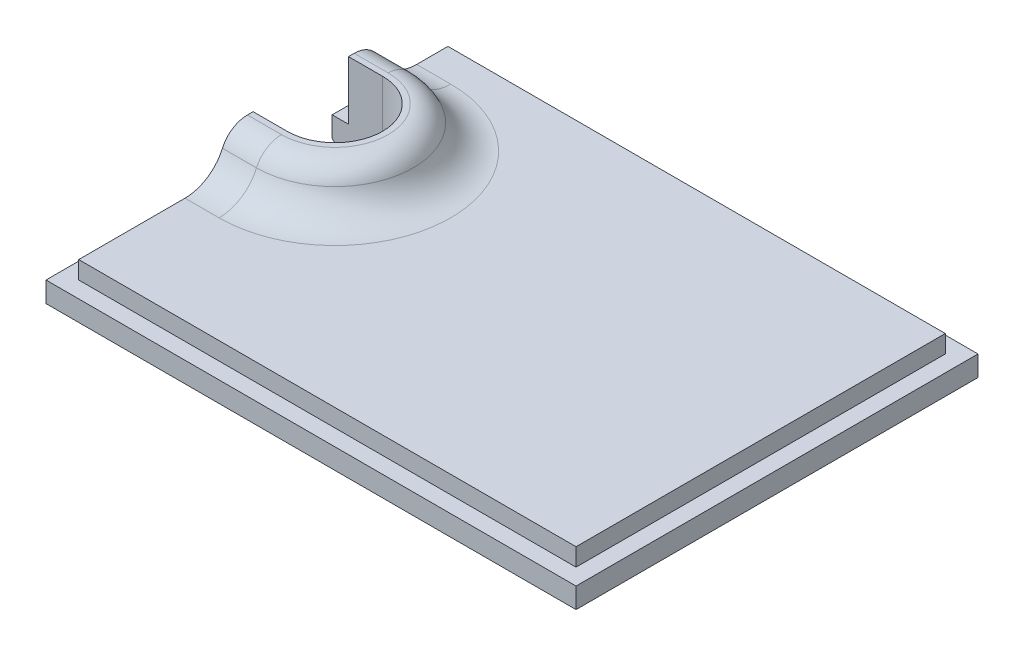
SolidWorks part; units mm, degrees
ref_plane "Front Plane" through (0, 0, 0) normal (0, 0, 1) x (1, 0, 0)
ref_plane "Top Plane" through (0, 0, 0) normal (0, 1, 0) x (1, 0, 0)
ref_plane "Right Plane" through (0, 0, 0) normal (1, 0, 0) x (0, 0, -1)
sketch "Sketch1" plane through (0, 0, 0) normal (0, 1, 0) x (1, 0, 0)
  line L0 (-19.45, 14.75) -> (-19.45, 6.25)
  line L1 (-19.45, -14.75) -> (19.45, -14.75)
  line L2 (19.45, -14.75) -> (19.45, 14.75)
  line L3 (19.45, 14.75) -> (-19.45, 14.75)
  line L4 (18.25, 13.55) -> (-18.25, 13.55)
  line L5 (-18.25, 13.55) -> (-18.25, 6.25)
  line L6 (-18.25, -13.55) -> (18.25, -13.55)
  line L7 (18.25, -13.55) -> (18.25, 13.55)
  line L8 (-18.25, 13.55) -> (0, 0) construction
  line L9 (0, 0) -> (18.25, -13.55) construction
  line L10 (0, 0) -> (18.25, 13.55) construction
  line L11 (0, 0) -> (-18.25, -13.55) construction
  line L12 (-15.75, 8.25) -> (-18.25, 8.25)
  line L13 (-18.25, 8.25) -> (-19.45, 8.25)
  line L14 (-15.75, 6.25) -> (-18.25, 6.25)
  line L15 (-18.25, 6.25) -> (-19.45, 6.25)
  line L16 (-15.75, -0.75) -> (-18.25, -0.75)
  line L17 (-18.25, -0.75) -> (-19.45, -0.75)
  line L18 (-15.75, -2.75) -> (-18.25, -2.75)
  line L19 (-18.25, -2.75) -> (-19.45, -2.75)
  line L20 (-19.45, -0.75) -> (-19.45, -14.75)
  line L21 (-19.45, 14.75) -> (-19.45, -14.75) construction
  line L22 (-18.25, -0.75) -> (-18.25, -13.55)
  line L23 (-18.25, 13.55) -> (-18.25, -13.55) construction
  arc A0 (-15.75, 6.25) -> (-15.75, -0.75) centre (-15.75, 2.75) cw
  arc A1 (-15.75, 8.25) -> (-15.75, -2.75) centre (-15.75, 2.75) cw
  arc A2 (-17.6698, 5.6765) -> (-15.75, -0.75) centre (-15.75, 2.75) cw construction
  arc A3 (-18.7669, 7.3487) -> (-15.75, -2.75) centre (-15.75, 2.75) cw construction
  dimension "D4" = 3.5
  dimension "D6" = 2
  dimension "D1" = 29.5
  dimension "D2" = 38.9
  dimension "D5" = 12
  dimension "D7" = 2.5
  dimension "D3" = 1.2
extrude "Boss-Extrude1" add sketch "Sketch1" along normal blind 1 contours L12 A1 L18 L5 L6 L7 L4 | A1 L12 L5 L14 A0 L16 L18 | L19 L5 L17 L0 | L15 L5 L13 L0 | L5 L19 L0 L1 L2 L3 L13 L4 L7 L6 | L17 L20 L1 L2 L3 L0 L15 L14 A0 L16 | L4 L5 L6 L7 region at (0, 0, -14.2618) region at (-18.85, 0, -7.25) region at (-17, 0, -8.114) region at (1.2088, 0, 0.2257) region at (-18.85, 0, 1.75)
extrude "Boss-Extrude2" add sketch "Sketch1<5>" along normal blind 1.6 from surface contours L5 A1 L6 L7 L4 | A1 L5 A0 | A1 L0 A0 L5 | L0 A1 L5 L4 L7 L6 L1 L2 L3 | A1 L5 A0 L0 | L5 L0 | L5 L0 | L22 L17 L20 L19 region at (0, 0, -14.2618) region at (-18.85, 0, -7.25) region at (-17, 0, -8.114) region at (1.2088, 0, 0.2257) region at (-18.85, 0, 1.75) starting at face at (-8.3625, 1, -1.375)
sketch "Sketch1<5>" plane through (0, 0, 0) normal (0, 1, 0) x (1, 0, 0) same geometry as "Sketch1"
extrude "Boss-Extrude3" add sketch "Sketch1<6>" along normal blind 1.3 from surface contours L5 A1 L6 L7 L4 | A1 L5 A0 region at (-17, 0, -8.114) region at (1.2088, 0, 0.2257) starting at face at (-8.3625, 2.6, -1.375)
sketch "Sketch1<6>" plane through (0, 0, 0) normal (0, 1, 0) x (1, 0, 0) same geometry as "Sketch1"
extrude "Boss-Extrude4" add sketch "Sketch1<8>" along normal blind 3 from surface contours A1 L5 A0 region at (-17, 0, -8.114) starting at face at (-8.0625, 3.9, -1.375)
sketch "Sketch1<8>" plane through (0, 0, 0) normal (0, 1, 0) x (1, 0, 0) same geometry as "Sketch1"
chamfer "Chamfer1" distance 1.1 angle 45 4 edges at (0, 0, -14.75) (19.45, 0, 0) (0, 0, 14.75) (-19.45, 0, -10.5)
fillet "Fillet1" radius 3 3 edges at (-17, 3.9, 2.75) (-17, 3.9, -8.25) (-10.25, 3.9, -2.75)
fillet "Fillet2" radius 2 3 edges at (-17, 6.9, -8.25) (-17, 6.9, 2.75) (-10.25, 6.9, -2.75)
